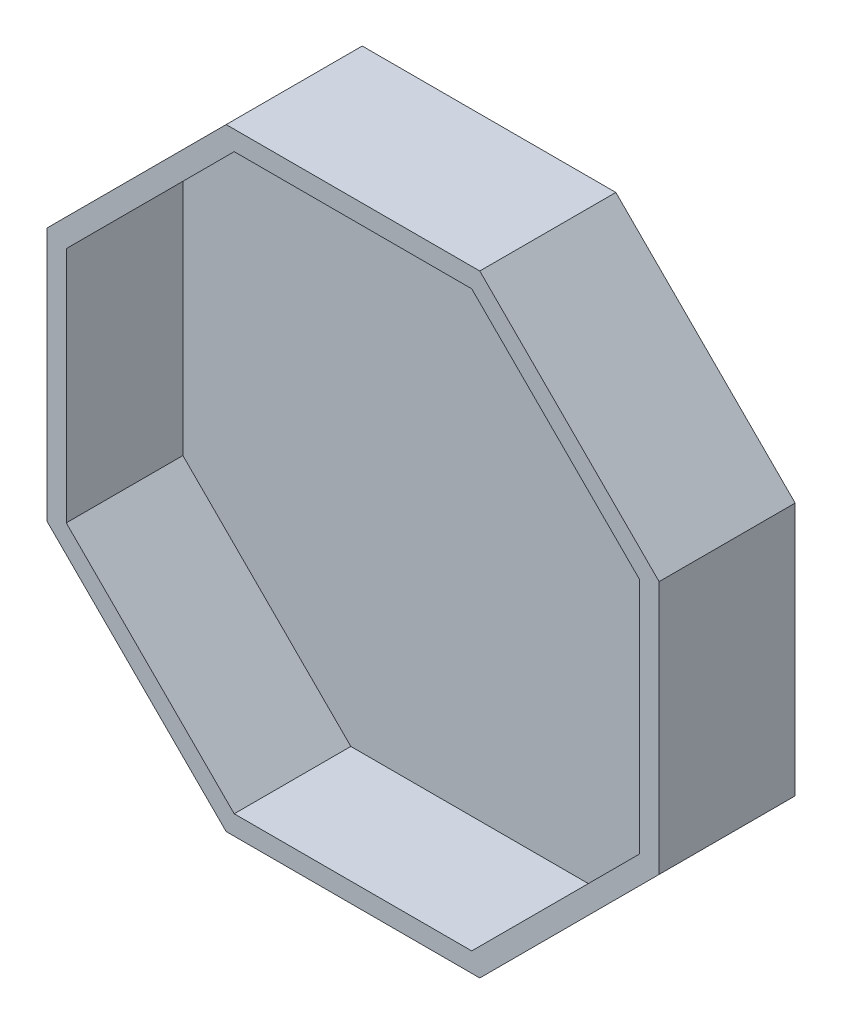
SolidWorks part; units mm, degrees
ref_plane "Front Plane" through (0, 0, 0) normal (0, 0, 1) x (1, 0, 0)
ref_plane "Top Plane" through (0, 0, 0) normal (0, 1, 0) x (1, 0, 0)
ref_plane "Right Plane" through (0, 0, 0) normal (1, 0, 0) x (0, 0, -1)
sketch "Sketch1" plane through (0, 0, 0) normal (0, 0, 1) x (1, 0, 0)
  line L1 (31.5, -13.0477) -> (31.5, 13.0477)
  line L2 (31.5, 13.0477) -> (13.0477, 31.5)
  line L3 (13.0477, 31.5) -> (-13.0477, 31.5)
  line L4 (-13.0477, 31.5) -> (-31.5, 13.0477)
  line L5 (-31.5, 13.0477) -> (-31.5, -13.0477)
  line L6 (-31.5, -13.0477) -> (-13.0477, -31.5)
  line L7 (-13.0477, -31.5) -> (13.0477, -31.5)
  line L8 (13.0477, -31.5) -> (31.5, -13.0477)
  circle A0 centre (0, 0) radius 31.5 construction
  point P1 (36.8254, -11.9683)
  point P12 (31.5, -13.0477)
  dimension "D1" = 63
extrude "Boss-Extrude1" add sketch "Sketch1" along normal blind 14
shell "Shell1" thickness 2 removed face at (0, 0, 14)
